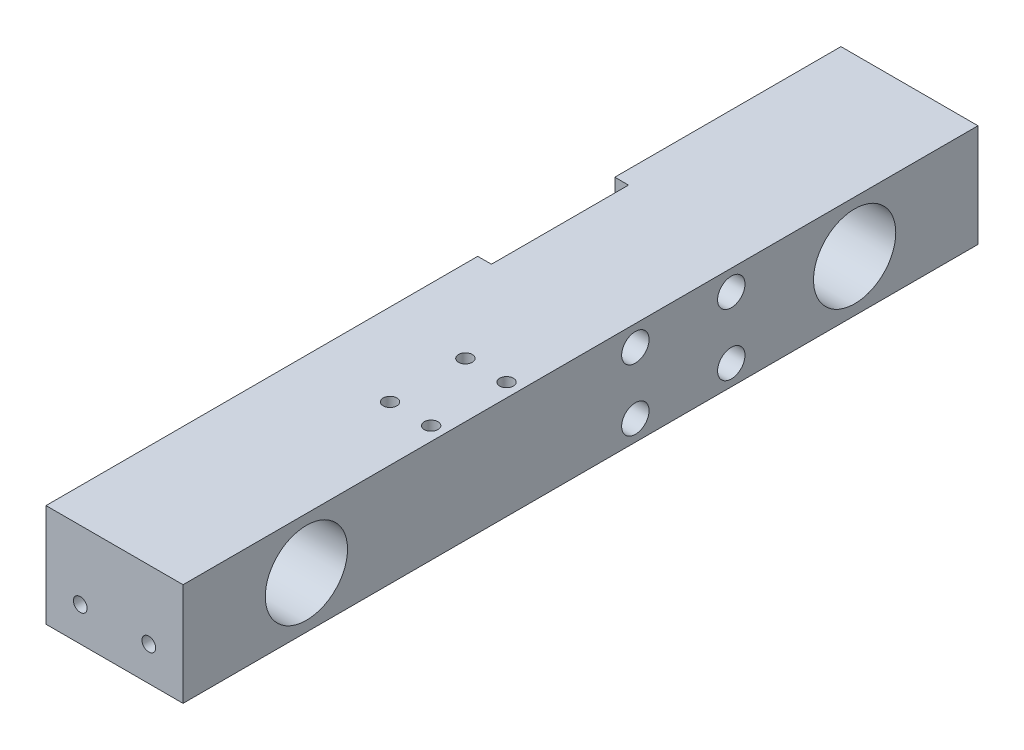
SolidWorks part; units mm, degrees
ref_plane "Front Plane" through (0, 0, 0) normal (0, 0, 1) x (1, 0, 0)
ref_plane "Top Plane" through (0, 0, 0) normal (0, 1, 0) x (1, 0, 0)
ref_plane "Right Plane" through (0, 0, 0) normal (1, 0, 0) x (0, 0, -1)
sketch "Sketch1" plane through (0, 0, 0) normal (0, 0, 1) x (1, 0, 0)
  line L0 (10, 0) -> (10, 15)
  line L1 (0, 0) -> (20, 0)
  line L2 (0, 0) -> (0, 15)
  line L3 (0, 15) -> (20, 15)
  line L4 (20, 0) -> (20, 15)
  circle A1 centre (15, 5) radius 1
  circle A2 centre (5, 5) radius 1
  point P9 (20, 7.5)
  dimension "D1" = 20
  dimension "D5" = 5
  dimension "D4" = 2
  dimension "D2" = 15
  dimension "D3" = 10
extrude "Boss-Extrude1" add sketch "Sketch1" along normal blind 116 contours L3 L4 L1 L2
ref_plane "Plane1" through (0, 0, 0) normal (0, 0, 1) x (1, 0, 0)
extrude "Cut-Extrude1" cut sketch "Sketch1<5>" along normal blind 10 contours A1 | A2
sketch "Sketch1<5>" plane through (0, 0, 0) normal (0, 0, 1) x (1, 0, 0) same geometry as "Sketch1"
ref_plane "Plane2" through (0, 0, 116) normal (0, 0, 1) x (1, 0, 0)
sketch "Sketch4" plane through (0, 0, 116) normal (0, 0, 1) x (1, 0, 0)
  line L0 (0, 15) -> (20, 15) construction
  line L1 (0, -55) -> (0, 55) construction
  line L2 (10, 15) -> (10, 0)
  line L3 (55, 0) -> (-55, 0) construction
  circle A0 centre (5, 5) radius 1
  circle A1 centre (15, 5) radius 1
  dimension "D1" = 2
  dimension "D2" = 10
  dimension "D3" = 5
extrude "Cut-Extrude2" cut sketch "Sketch4" against normal blind 10 contours A1 | A0
ref_plane "Plane4" through (20, 0, 0) normal (1, 0, 0) x (0, 0, -1)
sketch "Sketch5" plane through (20, 0, 0) normal (1, 0, 0) x (0, 0, -1)
  line L0 (-58, 15) -> (-58, 0)
  line L1 (-116, 15) -> (0, 15) construction
  line L2 (55, 0) -> (-55, 0) construction
  line L3 (-116, 8.25) -> (-116, -8.25) construction
  circle A0 centre (-98, 7.5) radius 2.5
  circle A1 centre (-18, 7.5) radius 2.5
  dimension "D1" = 5
  dimension "D2" = 18
  dimension "D3" = 7.5
extrude "Cut-Extrude3" cut sketch "Sketch5" against normal through all contours A0 | A1 region at (20, 7.5, 98) region at (20, 7.5, 18)
ref_plane "Plane5" through (20, 0, 0) normal (1, 0, 0) x (0, 0, -1)
sketch "Sketch6" plane through (20, 0, 0) normal (1, 0, 0) x (0, 0, -1)
  line L2 (-58, 15) -> (-58, 0)
  line L3 (-116, 15) -> (0, 15) construction
  line L4 (55, 0) -> (-55, 0) construction
  circle A0 centre (-98, 7.5) radius 6
  circle A1 centre (-18, 7.5) radius 6
  dimension "D1" = 12
extrude "Cut-Extrude4" cut sketch "Sketch6" against normal through all contours A0 | A1 region at (20, 7.5, 98) region at (20, 7.5, 18)
ref_plane "Plane6" through (0, 15, 0) normal (0, 1, 0) x (1, 0, 0)
sketch "Sketch8" plane through (0, 15, 0) normal (0, 1, 0) x (1, 0, 0)
  line L0 (10, -72.3) -> (20, -72.3)
  line L1 (10, -64.8) -> (20, -64.8)
  line L2 (10, -64.8) -> (10, -79.8)
  line L3 (10, -79.8) -> (20, -79.8)
  line L4 (20, -64.8) -> (20, -79.8)
  line L5 (15, -64.8) -> (15, -79.8)
  line L6 (0, -55) -> (0, 55) construction
  line L7 (-8.25, -116) -> (8.25, -116) construction
  circle A0 centre (12, -66.8) radius 1
  circle A1 centre (18, -66.8) radius 1
  circle A2 centre (18, -77.8) radius 1
  circle A3 centre (12, -77.8) radius 1
  dimension "D3" = 2
  dimension "D1" = 15
  dimension "D2" = 10
  dimension "D4" = 2
  dimension "D5" = 2
  dimension "D6" = 10
  dimension "D7" = 51.2
extrude "Cut-Extrude5" cut sketch "Sketch8" against normal through all contours A0 | A3 | A2 | A1
ref_plane "Plane7" through (0, 0, 0) normal (0, -1, 0) x (-1, 0, 0)
sketch "Sketch9" plane through (0, 0, 0) normal (0, -1, 0) x (-1, 0, 0)
  circle A0 centre (-18, -66.8) radius 1.5
  circle A1 centre (-18, -77.8) radius 1.5
  circle A2 centre (-12, -77.8) radius 1.5
  circle A3 centre (-12, -66.8) radius 1.5
  dimension "D1" = 3
  dimension "D2" = 3
  dimension "D3" = 3
  dimension "D4" = 3
extrude "Cut-Extrude6" cut sketch "Sketch9" against normal blind 5 contours A0 | A3 | A1 | A2
ref_plane "Plane8" through (0, 0, 0) normal (-1, 0, 0) x (0, 0, 1)
sketch "Sketch10" plane through (0, 0, 0) normal (-1, 0, 0) x (0, 0, 1)
  line L0 (-11, 0) -> (11, 0) construction
  line L1 (33, 0) -> (53, 0)
  line L2 (33, 0) -> (33, 15)
  line L3 (33, 15) -> (53, 15)
  line L4 (53, 0) -> (53, 15)
  line L5 (11, 15) -> (-11, 15) construction
  line L6 (43, 15) -> (43, 0)
  line L7 (33, 7.5) -> (53, 7.5)
  circle A0 centre (18, 7.5) radius 6 construction
  circle A2 centre (36, 12) radius 1
  circle A3 centre (50, 12) radius 1
  circle A4 centre (50, 3) radius 1
  circle A5 centre (36, 3) radius 1
  dimension "D2" = 15
  dimension "D3" = 2
  dimension "D4" = 3
  dimension "D5" = 3
  dimension "D1" = 20
extrude "Cut-Extrude7" cut sketch "Sketch10" against normal through all contours A2 | A3 | A4 | A5 region at (0, 12, 36) region at (0, 12, 50) region at (0, 3, 50) region at (0, 3, 36)
ref_plane "Plane9" through (20, 0, 0) normal (1, 0, 0) x (0, 0, -1)
sketch "Sketch11" plane through (20, 0, 0) normal (1, 0, 0) x (0, 0, -1)
  circle A0 centre (-36, 12) radius 2
  circle A1 centre (-36, 3) radius 2
  circle A2 centre (-50, 3) radius 2
  circle A3 centre (-50, 12) radius 2
  dimension "D1" = 4
  dimension "D2" = 4
  dimension "D3" = 4
  dimension "D4" = 4
extrude "Cut-Extrude8" cut sketch "Sketch11" against normal blind 5
extrude "Cut-Extrude9" cut sketch "Sketch10<3>" against normal blind 2 contours L2 L7 L6 L3 A2 | L6 L7 L4 L3 A3 | L7 L6 L1 L4 A4 | L7 L2 L1 L6 A5 region at (0, 3.7828, 38.0874) region at (0, 3.7828, 47.9126) region at (0, 11.2172, 38.0874) region at (0, 11.2172, 47.9126)
sketch "Sketch10<3>" plane through (0, 0, 0) normal (-1, 0, 0) x (0, 0, 1) same geometry as "Sketch10"
